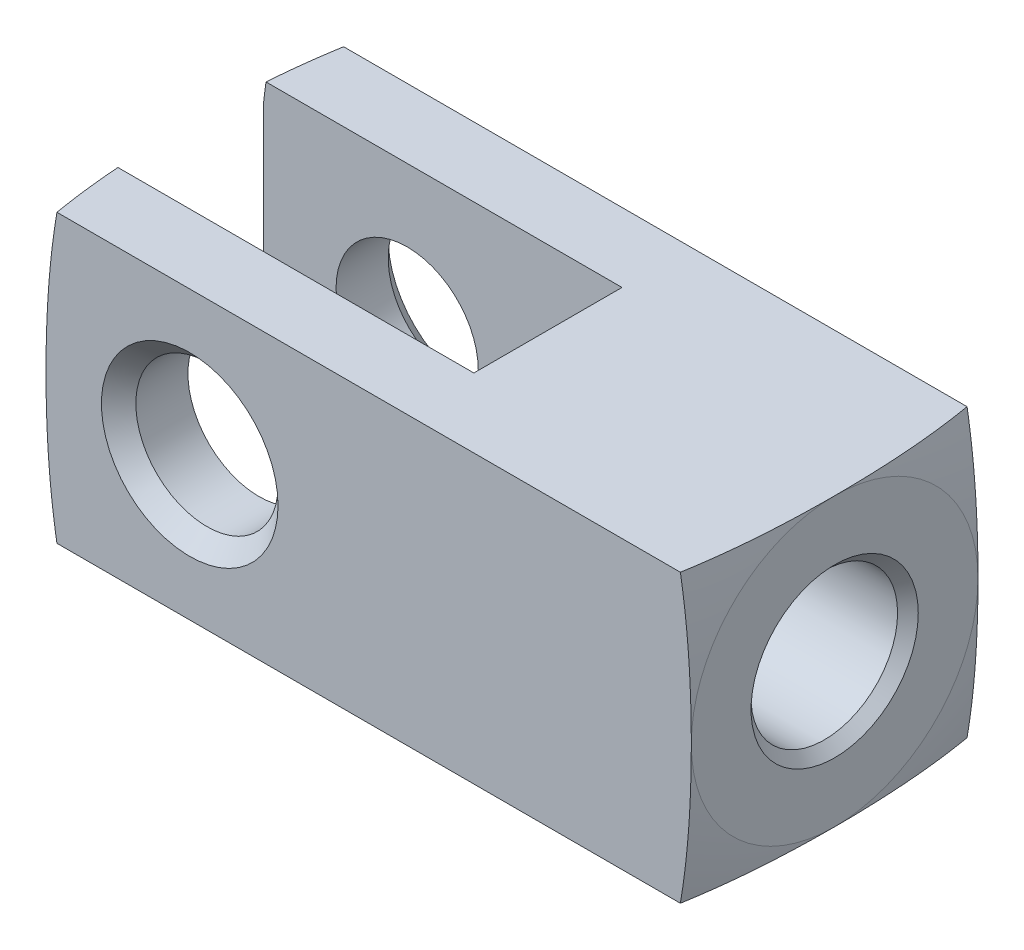
SolidWorks part; units mm, degrees
material "AISI 1045 Steel, cold drawn"
ref_plane "Front Plane" through (0, 0, 0) normal (0, 0, 1) x (1, 0, 0)
ref_plane "Top Plane" through (0, 0, 0) normal (0, 1, 0) x (1, 0, 0)
ref_plane "Right Plane" through (0, 0, 0) normal (1, 0, 0) x (0, 0, -1)
sketch "Sketch1" plane through (0, 0, 0) normal (0, 0, 1) x (1, 0, 0)
  line L0 (-9.5504, 9.525) -> (-9.5504, -9.525)
  line L1 (-9.5504, -9.525) -> (33.3248, -9.525)
  line L2 (33.3248, -9.525) -> (33.3248, 9.525)
  line L3 (33.3248, 9.525) -> (-9.5504, 9.525)
extrude "Boss-Extrude1" add sketch "Sketch1" against normal blind 9.525 and the other way blind 9.525
sketch "Sketch2" plane through (0, 0, 0) normal (0, 1, 0) x (1, 0, 0)
  line L0 (-9.5504, 4.9212) -> (-9.5504, -4.9212)
  line L1 (-9.5504, -4.9212) -> (14.2748, -4.9212)
  line L2 (14.2748, -4.9212) -> (14.2748, 4.9212)
  line L3 (14.2748, 4.9212) -> (-9.5504, 4.9212)
extrude "Cut-Extrude1" cut sketch "Sketch2" along normal blind 9.525 and the other way blind 9.525
hole_wizard "Hole1" positions "Sketch4" profile "Sketch3" legacy
sketch "Sketch4" plane through (33.3248, 0, 0) normal (1, 0, 0) x (0, 0, -1)
  point P0 (0, 0)
sketch "Sketch3" plane through (33.3248, 0, 0) normal (0, 1, 0) x (0, 0, -1)
  line L0 (0, 0) -> (0, 15.748)
  line L1 (0, 15.748) -> (4.8692, 15.748)
  line L2 (4.8692, 15.748) -> (4.8692, 0.6871)
  line L3 (4.8692, 0.6871) -> (5.5562, 0)
  line L4 (5.5562, 0) -> (0, 0)
  line L5 (0, -6.4453) -> (0, 115.525) construction
  line L6 (-4.8692, 0.6871) -> (-5.5562, 0) construction
  dimension "Diameter" = 9.7384
  dimension "Depth" = 15.748
  dimension "C-Sink Angle" = 90
  dimension "C-Sink Diameter" = 11.1125
cosmetic thread "Cosmetic Thread1" parameters "D1"=15.748, "D2"=11.1125
ref_plane "Plane1" through (0, 0, 6.35) normal (0, 0, 1) x (1, 0, 0)
ref_plane "Plane2" through (0, 0, -6.35) normal (0, 0, 1) x (1, 0, 0)
ref_plane "Plane3" through (23.876, 0, 0) normal (1, 0, 0) x (0, 0, -1)
hole_wizard "Hole2" positions "Sketch6" profile "Sketch5" legacy
sketch "Sketch6" plane through (17.5768, 0, 0) normal (1, 0, 0) x (0, 0, -1)
  point P0 (0, 0)
sketch "Sketch5" plane through (17.5768, 0, 0) normal (0, 1, 0) x (0, 0, -1)
  line L0 (0, 0) -> (0, 3.302)
  line L1 (0, 3.302) -> (4.9606, 3.302)
  line L2 (4.9606, 3.302) -> (4.9606, 0)
  line L3 (4.9606, 0) -> (0, 0)
  line L4 (0, 110) -> (0, -10) construction
  dimension "Diameter" = 9.9212
  dimension "Depth" = 3.302
sketch "Sketch7" plane through (0, 0, 0) normal (1, 0, 0) x (0, 0, -1)
  line L0 (-9.525, 0) -> (-9.525, 5.8674)
  line L1 (-9.525, 5.8674) -> (-8.382, 4.7244)
  line L2 (-8.382, 4.7244) -> (8.382, 4.7244)
  line L3 (8.382, 4.7244) -> (9.525, 5.8674)
  line L4 (9.525, 5.8674) -> (9.525, 0)
  line L5 (9.525, 0) -> (-9.525, 0)
  line L6 (9.525, 0) -> (-9.525, 0) construction
revolve "Cut-Revolve1" cut sketch "Sketch7" angle 360 about L6 reverse direction yes
sketch "Sketch8" plane through (0, 0, 0) normal (0, 0, 1) x (1, 0, 0)
  line L0 (33.3248, 0) -> (33.3248, 9.525)
  line L1 (30.7848, 19.05) -> (42.8498, 19.05)
  line L2 (42.8498, 19.05) -> (42.8498, 0)
  line L3 (42.8498, 0) -> (33.3248, 0)
  line L4 (42.8498, 0) -> (33.3248, 0) construction
  arc A0 (33.3248, 9.525) -> (30.7848, 19.05) centre (-3.664, 4.7625) ccw
revolve "Cut-Revolve2" cut sketch "Sketch8" angle 360 about L4 reverse direction yes
sketch "Sketch9" plane through (0, 0, 0) normal (0, 0, 1) x (1, 0, 0)
  line L0 (-19.0754, 0) -> (-19.0754, 19.05)
  line L1 (-19.0754, 19.05) -> (-7.0104, 19.05)
  line L2 (-9.5504, 9.525) -> (-9.5504, 0)
  line L3 (-9.5504, 0) -> (-19.0754, 0)
  line L4 (-9.5504, 0) -> (-19.0754, 0) construction
  arc A0 (-7.0104, 19.05) -> (-9.5504, 9.525) centre (27.4383, 4.7625) ccw
revolve "Cut-Revolve3" cut sketch "Sketch9" angle 360 about L4 reverse direction yes
ref_plane "Plane4" through (33.3248, 0, 0) normal (1, 0, 0) x (0, 0, -1)
ref_plane "Plane5" through (14.2748, 0, 0) normal (1, 0, 0) x (0, 0, -1)
ref_plane "dummy XY" through (0, 0, 0) normal (0, 0, 1) x (1, 0, 0)
ref_plane "dummy XZ" through (0, 0, 0) normal (0, -1, 0) x (-1, 0, 0)
ref_plane "dummy YZ" through (0, 0, 0) normal (1, 0, 0) x (0, 0, -1)
ref_axis "dummy X" through (-80.9, 0, 0) along (1, 0, 0)
ref_axis "dummy Y" through (0, -50, 0) along (0, 1, 0)
ref_axis "dummy Z" through (0, 0, 80.9) along (0, 0, -1)
sketch3d "dummy"
  point P0 (0, 0, 0)
ref_plane "h1 XY" through (0, 0, 0) normal (0, 0, 1) x (1, 0, 0)
ref_plane "h1 XZ" through (0, 9.525, 0) normal (0, -1, 0) x (-1, 0, 0)
ref_plane "h1 YZ" through (-9.5504, 0, 0) normal (1, 0, 0) x (0, 0, -1)
ref_axis "h1 X" through (-80.9, 9.525, 0) along (1, 0, 0)
ref_axis "h1 Y" through (-9.5504, -50, 0) along (0, 1, 0)
ref_axis "h1 Z" through (-9.5504, 9.525, 80.9) along (0, 0, -1)
sketch3d "h1"
  point P0 (-9.5504, 9.525, 0)
ref_plane "h2 XY" through (0, 0, 0) normal (0, 0, 1) x (1, 0, 0)
ref_plane "h2 XZ" through (0, -9.525, 0) normal (0, -1, 0) x (-1, 0, 0)
ref_plane "h2 YZ" through (-9.5504, 0, 0) normal (1, 0, 0) x (0, 0, -1)
ref_axis "h2 X" through (-80.9, -9.525, 0) along (1, 0, 0)
ref_axis "h2 Y" through (-9.5504, -50, 0) along (0, 1, 0)
ref_axis "h2 Z" through (-9.5504, -9.525, 80.9) along (0, 0, -1)
sketch3d "h2"
  point P0 (-9.5504, -9.525, 0)
ref_plane "l1 XY" through (0, 0, 0) normal (0, 0, 1) x (1, 0, 0)
ref_plane "l1 XZ" through (0, 9.525, 0) normal (0, -1, 0) x (-1, 0, 0)
ref_plane "l1 YZ" through (33.3248, 0, 0) normal (1, 0, 0) x (0, 0, -1)
ref_axis "l1 X" through (-80.9, 9.525, 0) along (1, 0, 0)
ref_axis "l1 Y" through (33.3248, -50, 0) along (0, 1, 0)
ref_axis "l1 Z" through (33.3248, 9.525, 80.9) along (0, 0, -1)
sketch3d "l1"
  point P0 (33.3248, 9.525, 0)
ref_plane "l11 XY" through (0, 0, 0) normal (0, 0, 1) x (1, 0, 0)
ref_plane "l11 XZ" through (0, 9.525, 0) normal (0, -1, 0) x (-1, 0, 0)
ref_plane "l11 YZ" through (33.3248, 0, 0) normal (1, 0, 0) x (0, 0, -1)
ref_axis "l11 X" through (-80.9, 9.525, 0) along (1, 0, 0)
ref_axis "l11 Y" through (33.3248, -50, 0) along (0, 1, 0)
ref_axis "l11 Z" through (33.3248, 9.525, 80.9) along (0, 0, -1)
sketch3d "l11"
  point P0 (33.3248, 9.525, 0)
ref_plane "l12 XY" through (0, 0, 0) normal (0, 0, 1) x (1, 0, 0)
ref_plane "l12 XZ" through (0, 9.525, 0) normal (0, -1, 0) x (-1, 0, 0)
ref_plane "l12 YZ" through (0, 0, 0) normal (1, 0, 0) x (0, 0, -1)
ref_axis "l12 X" through (-80.9, 9.525, 0) along (1, 0, 0)
ref_axis "l12 Y" through (0, -50, 0) along (0, 1, 0)
ref_axis "l12 Z" through (0, 9.525, 80.9) along (0, 0, -1)
sketch3d "l12"
  point P0 (0, 9.525, 0)
ref_plane "l2 XY" through (0, 0, 0) normal (0, 0, 1) x (1, 0, 0)
ref_plane "l2 XZ" through (0, 9.525, 0) normal (0, -1, 0) x (-1, 0, 0)
ref_plane "l2 YZ" through (-9.5504, 0, 0) normal (1, 0, 0) x (0, 0, -1)
ref_axis "l2 X" through (-80.9, 9.525, 0) along (1, 0, 0)
ref_axis "l2 Y" through (-9.5504, -50, 0) along (0, 1, 0)
ref_axis "l2 Z" through (-9.5504, 9.525, 80.9) along (0, 0, -1)
sketch3d "l2"
  point P0 (-9.5504, 9.525, 0)
ref_plane "l21 XY" through (0, 0, 0) normal (0, 1, 0) x (1, 0, 0)
ref_plane "l21 XZ" through (0, 0, 0) normal (0, 0, 1) x (1, 0, 0)
ref_plane "l21 YZ" through (33.3248, 0, 0) normal (1, 0, 0) x (0, 0, -1)
ref_axis "l21 X" through (-80.9, 0, 0) along (1, 0, 0)
ref_axis "l21 Y" through (33.3248, 0, 50) along (0, 0, -1)
ref_axis "l21 Z" through (33.3248, 50, 0) along (0, -1, 0)
sketch3d "l21"
  point P0 (33.3248, 0, 0)
ref_plane "l22 XY" through (0, 0, 0) normal (0, 1, 0) x (1, 0, 0)
ref_plane "l22 XZ" through (0, 0, 0) normal (0, 0, 1) x (1, 0, 0)
ref_plane "l22 YZ" through (14.2748, 0, 0) normal (1, 0, 0) x (0, 0, -1)
ref_axis "l22 X" through (-80.9, 0, 0) along (1, 0, 0)
ref_axis "l22 Y" through (14.2748, 0, 50) along (0, 0, -1)
ref_axis "l22 Z" through (14.2748, 50, 0) along (0, -1, 0)
sketch3d "l22"
  point P0 (14.2748, 0, 0)
ref_plane "piston_rod_clevis XY" through (33.3248, 0, 0) normal (1, 0, 0) x (0, 0, -1)
ref_plane "piston_rod_clevis XZ" through (0, 0, 0) normal (0, -1, 0) x (-1, 0, 0)
ref_plane "piston_rod_clevis YZ" through (0, 0, 0) normal (0, 0, -1) x (-1, 0, 0)
ref_axis "piston_rod_clevis X" through (33.3248, 0, 80.9) along (0, 0, -1)
ref_axis "piston_rod_clevis Y" through (33.3248, -50, 0) along (0, 1, 0)
ref_axis "piston_rod_clevis Z" through (80.9, 0, 0) along (-1, 0, 0)
sketch3d "piston_rod_clevis"
  point P0 (33.3248, 0, 0)
ref_plane "rod_clevis_body XY" through (0, 0, 0) normal (0, 0, 1) x (1, 0, 0)
ref_plane "rod_clevis_body XZ" through (0, 0, 0) normal (0, -1, 0) x (-1, 0, 0)
ref_plane "rod_clevis_body YZ" through (0, 0, 0) normal (1, 0, 0) x (0, 0, -1)
ref_axis "rod_clevis_body X" through (-80.9, 0, 0) along (1, 0, 0)
ref_axis "rod_clevis_body Y" through (0, -50, 0) along (0, 1, 0)
ref_axis "rod_clevis_body Z" through (0, 0, 80.9) along (0, 0, -1)
sketch3d "rod_clevis_body"
  point P0 (0, 0, 0)
ref_plane "th1 XY" through (0, 0, 0) normal (0, 0, 1) x (1, 0, 0)
ref_plane "th1 XZ" through (0, 5.5563, 0) normal (0, -1, 0) x (-1, 0, 0)
ref_plane "th1 YZ" through (33.3248, 0, 0) normal (1, 0, 0) x (0, 0, -1)
ref_axis "th1 X" through (-80.9, 5.5563, 0) along (1, 0, 0)
ref_axis "th1 Y" through (33.3248, -50, 0) along (0, 1, 0)
ref_axis "th1 Z" through (33.3248, 5.5563, 80.9) along (0, 0, -1)
sketch3d "th1"
  point P0 (33.3248, 5.5563, 0)
ref_plane "th2 XY" through (0, 0, 0) normal (0, 0, 1) x (1, 0, 0)
ref_plane "th2 XZ" through (0, -5.5563, 0) normal (0, -1, 0) x (-1, 0, 0)
ref_plane "th2 YZ" through (33.3248, 0, 0) normal (1, 0, 0) x (0, 0, -1)
ref_axis "th2 X" through (-80.9, -5.5563, 0) along (1, 0, 0)
ref_axis "th2 Y" through (33.3248, -50, 0) along (0, 1, 0)
ref_axis "th2 Z" through (33.3248, -5.5563, 80.9) along (0, 0, -1)
sketch3d "th2"
  point P0 (33.3248, -5.5563, 0)
ref_plane "to_cylinder XY" through (14.2748, 0, 0) normal (1, 0, 0) x (0, 0, -1)
ref_plane "to_cylinder XZ" through (0, 0, 0) normal (0, -1, 0) x (-1, 0, 0)
ref_plane "to_cylinder YZ" through (0, 0, 0) normal (0, 0, -1) x (-1, 0, 0)
ref_axis "to_cylinder X" through (14.2748, 0, 80.9) along (0, 0, -1)
ref_axis "to_cylinder Y" through (14.2748, -50, 0) along (0, 1, 0)
ref_axis "to_cylinder Z" through (80.9, 0, 0) along (-1, 0, 0)
sketch3d "to_cylinder"
  point P0 (14.2748, 0, 0)
ref_plane "w1 XY" through (0, 0, 0) normal (0, 1, 0) x (1, 0, 0)
ref_plane "w1 XZ" through (0, 0, -9.525) normal (0, 0, 1) x (1, 0, 0)
ref_plane "w1 YZ" through (33.3248, 0, 0) normal (1, 0, 0) x (0, 0, -1)
ref_axis "w1 X" through (-80.9, 0, -9.525) along (1, 0, 0)
ref_axis "w1 Y" through (33.3248, 0, 50) along (0, 0, -1)
ref_axis "w1 Z" through (33.3248, 50, -9.525) along (0, -1, 0)
sketch3d "w1"
  point P0 (33.3248, 0, -9.525)
ref_plane "w11 XY" through (0, 0, 0) normal (0, 1, 0) x (1, 0, 0)
ref_plane "w11 XZ" through (0, 0, -4.9212) normal (0, 0, 1) x (1, 0, 0)
ref_plane "w11 YZ" through (-9.5504, 0, 0) normal (1, 0, 0) x (0, 0, -1)
ref_axis "w11 X" through (-80.9, 0, -4.9212) along (1, 0, 0)
ref_axis "w11 Y" through (-9.5504, 0, 50) along (0, 0, -1)
ref_axis "w11 Z" through (-9.5504, 50, -4.9212) along (0, -1, 0)
sketch3d "w11"
  point P0 (-9.5504, 0, -4.9212)
ref_plane "w12 XY" through (0, 0, 0) normal (0, 1, 0) x (1, 0, 0)
ref_plane "w12 XZ" through (0, 0, 4.9212) normal (0, 0, 1) x (1, 0, 0)
ref_plane "w12 YZ" through (-9.5504, 0, 0) normal (1, 0, 0) x (0, 0, -1)
ref_axis "w12 X" through (-80.9, 0, 4.9212) along (1, 0, 0)
ref_axis "w12 Y" through (-9.5504, 0, 50) along (0, 0, -1)
ref_axis "w12 Z" through (-9.5504, 50, 4.9212) along (0, -1, 0)
sketch3d "w12"
  point P0 (-9.5504, 0, 4.9212)
ref_plane "w2 XY" through (0, 0, 0) normal (0, 1, 0) x (1, 0, 0)
ref_plane "w2 XZ" through (0, 0, 9.525) normal (0, 0, 1) x (1, 0, 0)
ref_plane "w2 YZ" through (33.3248, 0, 0) normal (1, 0, 0) x (0, 0, -1)
ref_axis "w2 X" through (-80.9, 0, 9.525) along (1, 0, 0)
ref_axis "w2 Y" through (33.3248, 0, 50) along (0, 0, -1)
ref_axis "w2 Z" through (33.3248, 50, 9.525) along (0, -1, 0)
sketch3d "w2"
  point P0 (33.3248, 0, 9.525)
